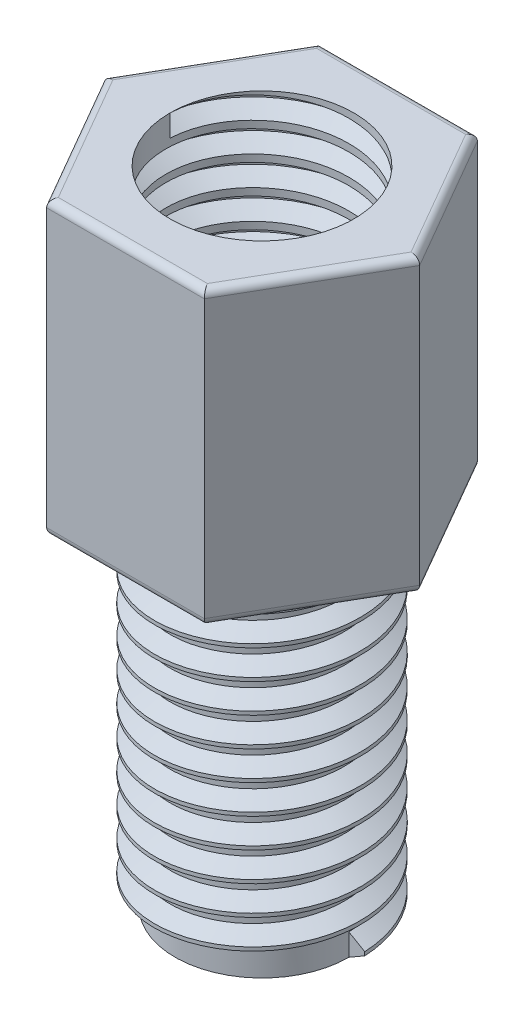
SolidWorks part; units mm, degrees
material "Brass"
ref_plane "Front Plane" through (0, 0, 0) normal (0, 0, 1) x (1, 0, 0)
ref_plane "Top Plane" through (0, 0, 0) normal (0, 1, 0) x (1, 0, 0)
ref_plane "Right Plane" through (0, 0, 0) normal (1, 0, 0) x (0, 0, -1)
sketch "Sketch1" plane through (0, 0, 0) normal (0, 1, 0) x (1, 0, 0)
  line L1 (2.702, 0) -> (1.351, 2.34)
  line L2 (1.351, 2.34) -> (-1.351, 2.34)
  line L3 (-1.351, 2.34) -> (-2.702, 0)
  line L4 (-2.702, 0) -> (-1.351, -2.34)
  line L5 (-1.351, -2.34) -> (1.351, -2.34)
  line L6 (1.351, -2.34) -> (2.702, 0)
  circle A0 centre (0, 0) radius 2.34 construction
  dimension "D1" = 4.68
extrude "Boss-Extrude1" add sketch "Sketch1" along normal blind 5
sketch "Sketch2" plane through (0, 5, 0) normal (0, 1, 0) x (1, 0, 0)
  circle A0 centre (0, 0) radius 1.49
  dimension "D1" = 2.98
extrude "Boss-Extrude2" add sketch "Sketch2" against normal blind 6 from surface starting at face at (0, 0, 0)
hole_wizard "Tap Drill for M3 Helicoil1" positions "Sketch4" profile "Sketch5" hole size "M3x0.5" standard "ANSI Metric"
sketch "Sketch4" plane through (0, 5, 0) normal (0, 1, 0) x (1, 0, 0)
  point P0 (0, 0)
sketch "Sketch5" plane through (0, 5, 0) normal (1, 0, 0) x (0, 0, 1)
  line L0 (0, 0) -> (0, 3.9464)
  line L1 (0, 3.9464) -> (1.575, 3)
  line L2 (1.575, 3) -> (1.575, 0)
  line L5 (1.575, 0) -> (0, 0)
  line L10 (0, 3.9464) -> (-1.575, 3) construction
  line L11 (0, -6.35) -> (0, 107.95) construction
  dimension "Hole Dia." = 3.15
  dimension "Hole Depth" = 3
  dimension "Drill Angle" = 118
thread "Thread1" pitch 0.5 method extrude profile "Thread Profile1" start angle 0, offset 0, length 0, pitch 0.5, diameter 2.98
ref_plane "Plane1" through (1.49, -6, 0) normal (0, 0, 1) x (1, 0, 0)
sketch "Thread Profile1" plane through (1.49, -6, 0) normal (0, 0, 1) x (1, 0, 0)
  line L0 (0, 0) -> (0, 0.5) construction
  line L1 (0, 0) -> (0.2706, 0.1562)
  line L2 (0.2706, 0.1562) -> (0.2706, 0.2187)
  line L3 (0.2706, 0.2187) -> (0, 0.375)
  line L4 (0.2706, 0.1875) -> (0, 0.1875) construction
  line L11 (0, 0) -> (0, 0.375)
  point P2 (0, 0)
  dimension "Pitch" = 0.5
  dimension "Profile_Angle" = 60
  dimension "Profile_Land" = 0.0625
  dimension "Profile_Height" = 0.2706
thread "Thread2" pitch 0.5 method cut profile "Thread Profile2" start angle 0, offset 0, length 0, pitch 0.5, diameter 3.15
ref_plane "Plane2" through (-1.575, 5, 0) normal (0, 0, 1) x (-1, 0, 0)
sketch "Thread Profile2" plane through (-1.575, 5, 0) normal (0, 0, 1) x (-1, 0, 0)
  line L0 (0, 0) -> (0, 0.5) construction
  line L1 (0, 0) -> (0.2706, 0.1562)
  line L2 (0.2706, 0.1562) -> (0.2706, 0.2187)
  line L3 (0.2706, 0.2187) -> (0, 0.375)
  line L4 (0.2706, 0.1875) -> (0, 0.1875) construction
  line L11 (0, 0) -> (0, 0.375)
  point P2 (0, 0)
  dimension "Pitch" = 0.5
  dimension "Profile_Angle" = 60
  dimension "Profile_Land" = 0.0625
  dimension "Profile_Height" = 0.2706
fillet "Fillet1" radius 0.127 12 edges at (-2.0265, 0, 1.17) (-2.0265, 0, -1.17) (0, 0, -2.34) (2.0265, 0, -1.17) (0, 0, 2.34) (2.0265, 0, 1.17) (2.0265, 5, -1.17) (0, 5, -2.34) (-2.0265, 5, -1.17) (-2.0265, 5, 1.17) (0, 5, 2.34) (2.0265, 5, 1.17)
